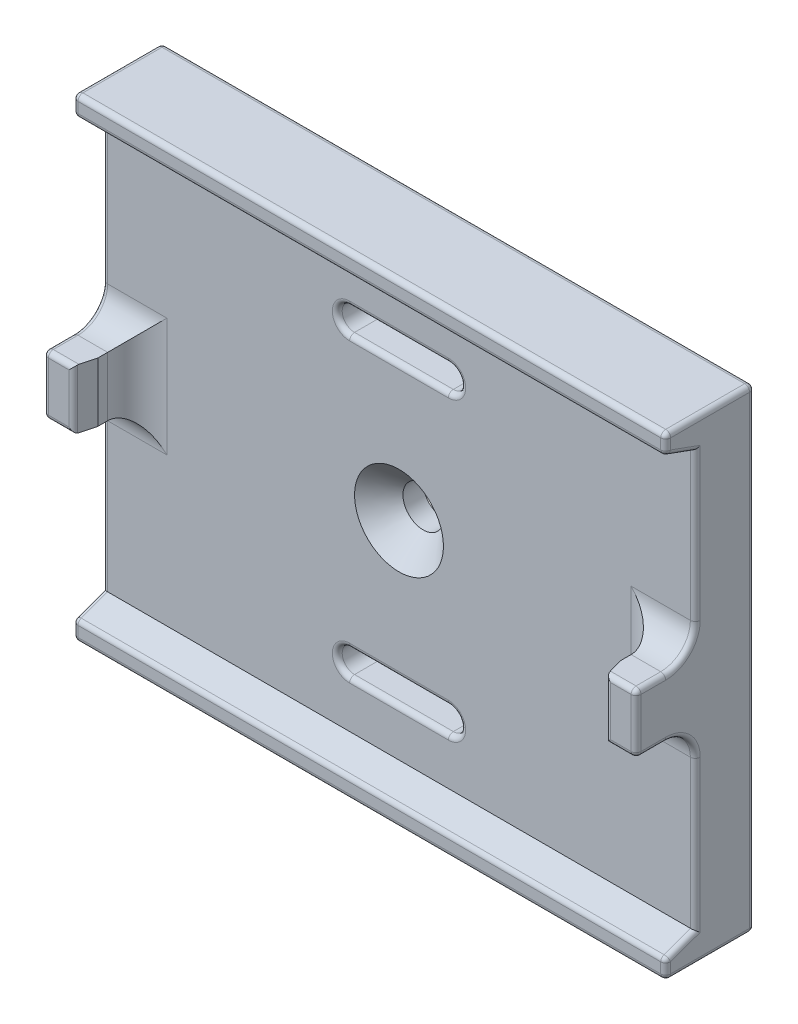
SolidWorks part; units mm, degrees
ref_plane "Ebene vorne" through (0, 0, 0) normal (0, 0, 1) x (1, 0, 0)
ref_plane "Ebene oben" through (0, 0, 0) normal (0, 1, 0) x (1, 0, 0)
ref_plane "Ebene rechts" through (0, 0, 0) normal (1, 0, 0) x (0, 0, -1)
sketch "Skizze1" plane through (0, 0, 0) normal (1, 0, 0) x (0, 0, -1)
  line L0 (0, -69.0302) -> (0, 78.9651) construction
  line L1 (-66.1487, 0) -> (60.4978, 0) construction
  line L2 (0, 48) -> (0, -48)
  line L3 (0, -48) -> (-18, -48)
  line L4 (-18, -48) -> (-18, -44.1838)
  line L5 (-18, -44.1838) -> (-12, -42)
  line L6 (-12, -42) -> (-12, 42)
  line L7 (-18, 44.1838) -> (-12, 42)
  line L8 (-18, 48) -> (-18, 44.1838)
  line L9 (0, 48) -> (-18, 48)
  point P12 (-12, 0)
  point P15 (0, 0)
  dimension "D1" = 96
  dimension "D2" = 84
  dimension "D3" = 6
  dimension "D4" = 12
  dimension "D5" = 110
  dimension "D6" = 88.3676
extrude "Aufsatz-Linear austragen1" add sketch "Skizze1" along normal blind 60 and the other way blind 60
hole_wizard "Formsenkung für M8 SFHCS1" positions "Skizze3" profile "Skizze2" countersink size "M8" standard "ANSI Metrisch" end condition through all
sketch "Skizze3" plane through (0, 0, 12) normal (0, 0, 1) x (1, 0, 0)
  point P0 (0, 0)
sketch "Skizze2" plane through (0, 0, 12) normal (1, 0, 0) x (0, -1, 0)
  line L0 (0, 0) -> (0, 12)
  line L1 (0, 12) -> (4.1, 12)
  line L2 (4.1, 12) -> (4.1, 4.9)
  line L3 (4.1, 4.9) -> (9, 0)
  line L5 (9, 0) -> (0, 0)
  line L6 (-4.1, 4.9) -> (-9, 0) construction
  line L11 (0, -6.35) -> (0, 107.95) construction
  dimension "Bohrerdurchmesser" = 8.2
  dimension "Bohrungstiefe" = 12
  dimension "Senkdurchmesser (Oben)" = 18
  dimension "Senkwinkel (Oben)" = 90
sketch "Skizze4" plane through (0, 0, 0) normal (0, 0, -1) x (-1, 0, 0)
  line L0 (-77.5584, 0) -> (72.4313, 0) construction
  line L1 (0, -67.9859) -> (0, 71.3457) construction
  line L2 (18.25, -20.25) -> (-18.25, -20.25)
  line L3 (-20.25, -18.25) -> (-20.25, 18.25)
  line L4 (18.25, 20.25) -> (-18.25, 20.25)
  line L5 (20.25, -18.25) -> (20.25, 18.25)
  arc A0 (-20.25, -18.25) -> (-18.25, -20.25) centre (-18.25, -18.25) ccw
  arc A1 (-20.25, 18.25) -> (-18.25, 20.25) centre (-18.25, 18.25) cw
  arc A2 (20.25, 18.25) -> (18.25, 20.25) centre (18.25, 18.25) ccw
  arc A3 (20.25, -18.25) -> (18.25, -20.25) centre (18.25, -18.25) cw
  point P8 (0, -20.25)
  point P13 (-20.25, 0)
  point P20 (20.25, 0)
  point P21 (0, 20.25)
  dimension "D1" = 2
  dimension "D2" = 40.5
  dimension "D3" = 40.5
extrude "Schnitt-Linear austragen1" cut sketch "Skizze4" against normal blind 3
sketch "Skizze5" plane through (0, 0, 12) normal (0, 0, 1) x (1, 0, 0)
  line L0 (0, 69.9414) -> (0, -54.024) construction
  line L1 (-72.815, 0) -> (77.6266, 0) construction
  line L2 (-60, -6) -> (-60, 6)
  line L3 (-60, 42) -> (-60, -42) construction
  line L4 (-60, 6) -> (-53, 6)
  line L5 (-53, 6) -> (-53, -6)
  line L6 (-60, -6) -> (-53, -6)
  line L7 (60, -6) -> (53, -6)
  line L8 (53, 6) -> (53, -6)
  line L9 (60, 6) -> (53, 6)
  line L10 (60, -6) -> (60, 6)
  point P5 (60, 0)
  point P12 (-53, 0)
  point P13 (-60, 0)
  point P14 (53, 0)
  dimension "D1" = 106
  dimension "D2" = 12
extrude "Aufsatz-Linear austragen2" add sketch "Skizze5" along normal blind 12
chamfer "Fase1" distance 4 angle 15 2 edges at (-53, 0, 24) (53, 0, 24) first distance on face at (-53, 0, 18) first distance on face at (53, 0, 18)
fillet "Verrundung1" radius 6 6 edges at (56.5, -6, 12) (56.5, 6, 12) (-56.5, 6, 12) (-56.5, -6, 12) (-53, 0, 12) (53, 0, 12)
sketch "Skizze6" plane through (0, 0, 12) normal (0, 0, 1) x (1, 0, 0)
  line L0 (0, 61.7821) -> (0, -52.3331) construction
  line L1 (-71.142, 0) -> (73.0723, 0) construction
  line L2 (-10, 30) -> (10, 30) construction
  line L3 (-10, 32.5) -> (10, 32.5)
  line L4 (-10, 27.5) -> (10, 27.5)
  line L5 (-10, -30) -> (10, -30) construction
  line L6 (-10, -32.5) -> (10, -32.5)
  line L7 (-10, -27.5) -> (10, -27.5)
  arc A0 (-10, 32.5) -> (-10, 27.5) centre (-10, 30) ccw
  arc A1 (10, 27.5) -> (10, 32.5) centre (10, 30) ccw
  arc A2 (-10, -32.5) -> (-10, -27.5) centre (-10, -30) cw
  arc A3 (10, -27.5) -> (10, -32.5) centre (10, -30) cw
  point P7 (0, 30)
  point P14 (0, -30)
  dimension "D1" = 60
  dimension "D2" = 5
  dimension "D3" = 20
extrude "Schnitt-Linear austragen2" cut sketch "Skizze6" against normal blind 12
fillet "Verrundung2" radius 1 56 edges at (60, -27, 12) (60, -7.7574, 13.7574) (60, 27, 12) (60, 7.7574, 13.7574) (-60, 6, 21) (-60, 27, 12) (-60, -27, 12) (-60, -6, 21) (60, 0, 24) (57.0359, -6, 24) (54.0718, 0, 24) (57.0359, 6, 24) (-60, 0, 24) (-57.0359, 6, 24) (-54.0718, 0, 24) (-57.0359, -6, 24) (0, 48, 18) (-60, 46.0919, 18) (0, 44.1838, 18) (60, 46.0919, 18) (60, -46.0919, 18) (-60, -46.0919, 18) (0, -44.1838, 18) (0, -48, 18) (-60, -48, 9) (-60, 48, 9) (-60, 0, 0) (0, -48, 0) (60, -48, 9) (60, 48, 9) (60, 0, 0) (0, 48, 0) (60, -6, 21) (60, 6, 21) (-60, 7.7574, 13.7574) (-60, -7.7574, 13.7574) (12.5, 30, 0) (0, 27.5, 0) (-12.5, 30, 0) (12.5, -30, 0) (0, -32.5, 0) (-12.5, -30, 0) (-12.5, 30, 12) (0, 32.5, 12) (12.5, 30, 12) (12.5, -30, 12) (0, -32.5, 12) (-12.5, -30, 12) (0, 32.5, 0) (0, -27.5, 0) (0, 27.5, 12) (0, -27.5, 12) (60, -43.0919, 15) (60, 43.0919, 15) (-60, -43.0919, 15) (-60, 43.0919, 15)
